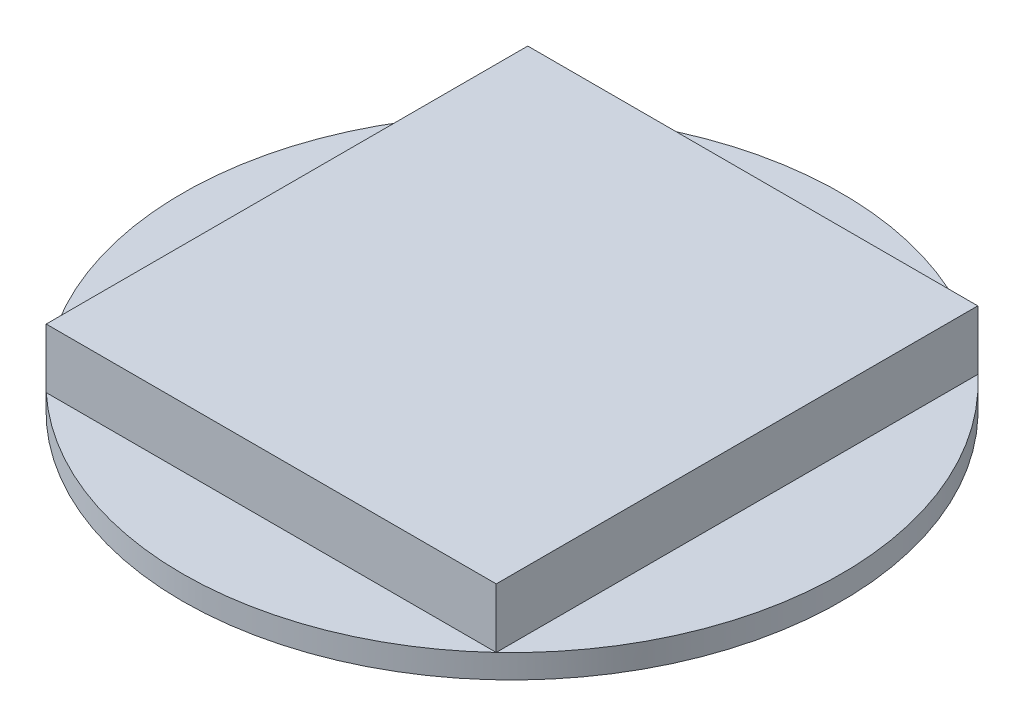
SolidWorks part; units mm, degrees
ref_plane "Front Plane" through (0, 0, 0) normal (0, 0, 1) x (1, 0, 0)
ref_plane "Top Plane" through (0, 0, 0) normal (0, 1, 0) x (1, 0, 0)
ref_plane "Right Plane" through (0, 0, 0) normal (1, 0, 0) x (0, 0, -1)
sketch "Sketch1" plane through (0, 0, 0) normal (0, 1, 0) x (1, 0, 0)
  circle A0 centre (0, 0) radius 277.5
  dimension "D1" = 555
extrude "Boss-Extrude1" add sketch "Sketch1" along normal blind 10 and the other way blind 10
sketch "Sketch2" plane through (0, 10, 0) normal (0, 1, 0) x (1, 0, 0)
  line L1 (189.4746, -202.7452) -> (-189.4746, -202.7452)
  line L2 (189.4746, -202.7452) -> (189.4746, 202.7452)
  line L3 (189.4746, 202.7452) -> (-189.4746, 202.7452)
  line L4 (-189.4746, -202.7452) -> (-189.4746, 202.7452)
  line L5 (189.4746, -202.7452) -> (-189.4746, 202.7452) construction
  line L6 (189.4746, 202.7452) -> (-189.4746, -202.7452) construction
  circle A0 centre (0, 0) radius 277.5 construction
  point P0 (0, 0)
extrude "Boss-Extrude2" add sketch "Sketch2" along normal blind 50 contours L2 L1 L4 L3
